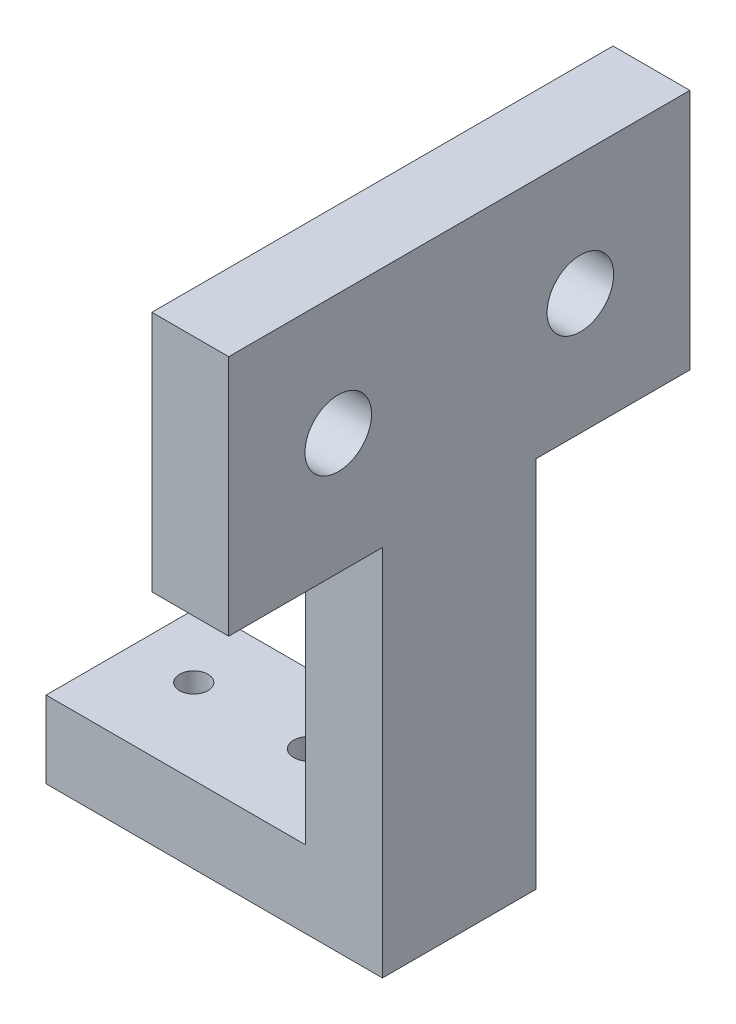
SolidWorks part; units mm, degrees
ref_plane "Front Plane" through (0, 0, 0) normal (0, 0, 1) x (1, 0, 0)
ref_plane "Top Plane" through (0, 0, 0) normal (0, 1, 0) x (1, 0, 0)
ref_plane "Right Plane" through (0, 0, 0) normal (1, 0, 0) x (0, 0, -1)
sketch "Sketch1" plane through (0, 0, 0) normal (0, 0, 1) x (1, 0, 0)
  line L0 (-13.8933, 0) -> (13.8933, 0)
  line L10 (13.8933, 50.8) -> (7.5433, 50.8)
  line L11 (7.5433, 50.8) -> (7.5433, 6.35)
  line L12 (7.5433, 6.35) -> (-13.8933, 6.35)
  line L13 (-13.8933, 6.35) -> (-13.8933, 0)
  line L14 (13.8933, 50.8) -> (13.8933, 0)
  point P6 (0, 0)
  dimension "D1" = 27.7866
  dimension "D2" = 50.8
  dimension "D3" = 6.35
  dimension "D4" = 6.35
extrude "Boss-Extrude1" add sketch "Sketch1" along normal mid plane 12.7
sketch "Sketch2" plane through (7.5433, 0, 0) normal (-1, 0, 0) x (0, 0, 1)
  line L0 (6.35, 50.8) -> (-6.35, 50.8) construction
  line L1 (-19.05, 30.8) -> (19.05, 30.8)
  line L2 (-19.05, 30.8) -> (-19.05, 50.8)
  line L3 (-19.05, 50.8) -> (19.05, 50.8)
  line L4 (19.05, 30.8) -> (19.05, 50.8)
  line L5 (-19.05, 30.8) -> (19.05, 50.8) construction
  line L6 (-19.05, 50.8) -> (19.05, 30.8) construction
  point P0 (0, 40.8)
  point P5 (0, 50.8)
  point P8 (0, 50.8)
  dimension "D1" = 20
  dimension "D2" = 38.1
extrude "Boss-Extrude2" add sketch "Sketch2" against normal up to surface (6.35 mm away) up to face at (13.8933, 25.4, 0)
sketch "Sketch3" plane through (0, 6.35, 0) normal (0, 1, 0) x (1, 0, 0)
  arc A0 (0.3802, 1.825) -> (0.3802, -0.525) centre (0.8067, 0.65) ccw construction
  circle A1 centre (-8.6933, 0.65) radius 1.175 construction
  arc A2 (0.3802, 1.825) -> (0.3802, -0.525) centre (0.8067, 0.65) ccw
  circle A3 centre (-8.6933, 0.65) radius 1.175
  circle A4 centre (0.8067, 0.65) radius 1.25
extrude "Cut-Extrude1" cut sketch "Sketch3" against normal through all contours A2 A4 | A3 region at (0.8067, 6.35, -0.65) region at (-8.6933, 6.35, -0.65)
sketch "Sketch4" plane through (7.5433, 0, 0) normal (-1, 0, 0) x (0, 0, 1)
  line L0 (-10, 40.8) -> (10, 40.8) construction
  line L1 (-19.05, 30.8) -> (19.05, 50.8) construction
  circle A0 centre (-10, 40.8) radius 2.75
  circle A1 centre (10, 40.8) radius 2.75
  point P6 (0, 40.8)
  point P9 (0, 40.8)
  dimension "D1" = 5.5
  dimension "D2" = 20
extrude "Cut-Extrude2" cut sketch "Sketch4" against normal through all
